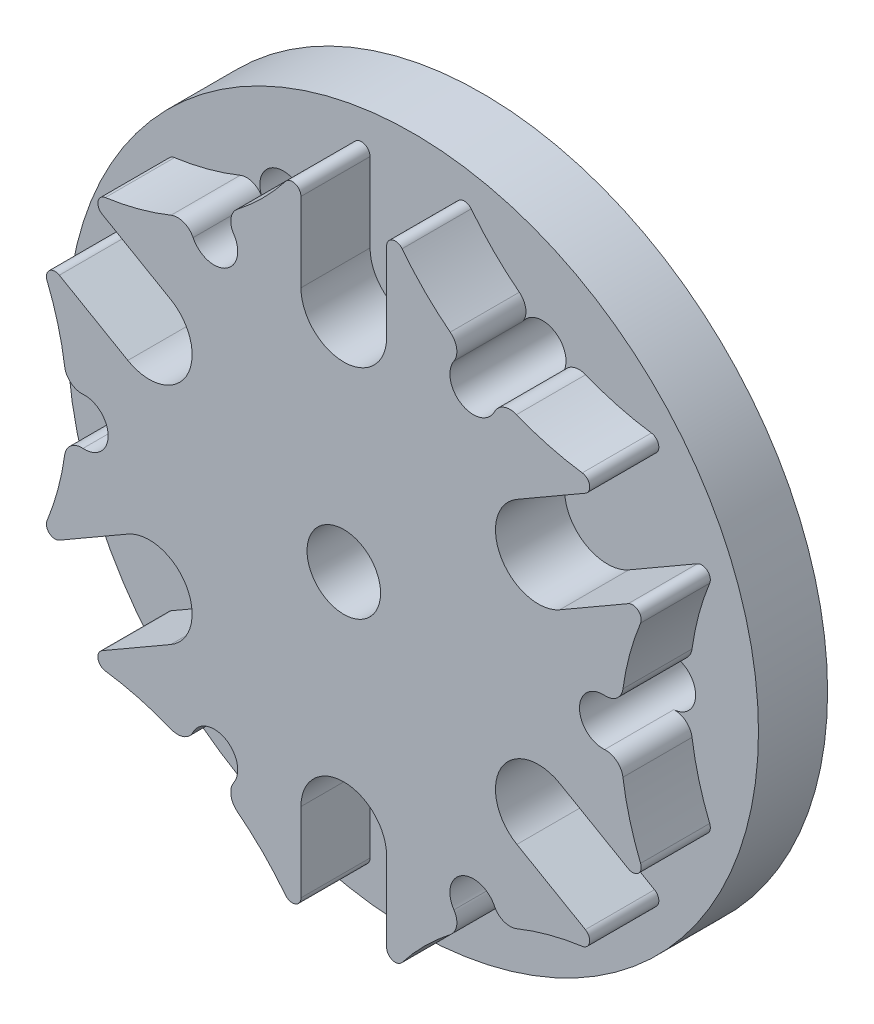
SolidWorks part; units mm, degrees
ref_plane "Front Plane" through (0, 0, 0) normal (0, 0, 1) x (1, 0, 0)
ref_plane "Top Plane" through (0, 0, 0) normal (0, 1, 0) x (1, 0, 0)
ref_plane "Right Plane" through (0, 0, 0) normal (1, 0, 0) x (0, 0, -1)
sketch "Sketch2" plane through (0, 0, 0) normal (0, 0, 1) x (1, 0, 0)
  circle A0 centre (0, 0) radius 31.75
  point P17 (0, 0)
  dimension "D4" = 63.5
extrude "Boss-Extrude1" add sketch "Sketch2" along normal blind 6.35
sketch "Sketch3" plane through (0, 0, 6.35) normal (0, 0, 1) x (1, 0, 0)
  line L0 (0, 30.411) -> (0, 20.6375) construction
  line L1 (3.937, 30.411) -> (3.937, 20.6375)
  line L2 (-3.937, 30.411) -> (-3.937, 20.6375)
  line L5 (24.3682, 18.6151) -> (15.9041, 13.7283)
  line L8 (28.3052, 11.796) -> (19.8411, 6.9092)
  line L11 (26.3367, 15.2055) -> (17.8726, 10.3187) construction
  line L14 (28.3052, -11.796) -> (19.8411, -6.9092)
  line L17 (24.3682, -18.6151) -> (15.9041, -13.7283)
  line L18 (26.3367, -15.2055) -> (17.8726, -10.3187) construction
  line L19 (3.937, -30.411) -> (3.937, -20.6375)
  line L20 (-3.937, -30.411) -> (-3.937, -20.6375)
  line L21 (0, -30.411) -> (0, -20.6375) construction
  line L22 (-24.3682, -18.6151) -> (-15.9041, -13.7283)
  line L23 (-28.3052, -11.796) -> (-19.8411, -6.9092)
  line L24 (-26.3367, -15.2055) -> (-17.8726, -10.3188) construction
  line L25 (-28.3052, 11.796) -> (-19.8411, 6.9092)
  line L26 (-24.3682, 18.6151) -> (-15.9041, 13.7283)
  line L27 (-26.3367, 15.2055) -> (-17.8726, 10.3187) construction
  circle A0 centre (0, 0) radius 20.6375 construction
  arc A1 (3.937, 30.411) -> (-3.937, 30.411) centre (0, 30.411) ccw
  arc A2 (-3.937, 20.6375) -> (3.937, 20.6375) centre (0, 20.6375) ccw
  arc A13 (-3.937, 30.411) -> (-24.3682, 18.6151) centre (-25.4, 43.9941) cw
  arc A14 (28.3052, 11.796) -> (24.3682, 18.6151) centre (26.3367, 15.2055) ccw
  arc A15 (15.9041, 13.7283) -> (19.8411, 6.9092) centre (17.8726, 10.3187) ccw
  arc A16 (24.3682, -18.6151) -> (28.3052, -11.796) centre (26.3367, -15.2055) ccw
  arc A17 (19.8411, -6.9092) -> (15.9041, -13.7283) centre (17.8726, -10.3187) ccw
  arc A18 (-3.937, -30.411) -> (3.937, -30.411) centre (0, -30.411) ccw
  arc A19 (3.937, -20.6375) -> (-3.937, -20.6375) centre (0, -20.6375) ccw
  arc A20 (-28.3052, -11.796) -> (-24.3682, -18.6151) centre (-26.3367, -15.2055) ccw
  arc A21 (-15.9041, -13.7283) -> (-19.8411, -6.9092) centre (-17.8726, -10.3188) ccw
  arc A22 (-24.3682, 18.6151) -> (-28.3052, 11.796) centre (-26.3367, 15.2055) ccw
  arc A23 (-19.8411, 6.9092) -> (-15.9041, 13.7283) centre (-17.8726, 10.3187) ccw
  arc A24 (24.3682, 18.6151) -> (3.937, 30.411) centre (25.4, 43.9941) cw
  arc A25 (28.3052, -11.796) -> (28.3052, 11.796) centre (50.8, 0) cw
  arc A26 (3.937, -30.411) -> (24.3682, -18.6151) centre (25.4, -43.9941) cw
  arc A27 (-24.3682, -18.6151) -> (-3.937, -30.411) centre (-25.4, -43.9941) cw
  arc A28 (-28.3052, 11.796) -> (-28.3052, -11.796) centre (-50.8, 0) cw
  point P5 (0, 25.5243)
  point P10 (-12.7, 21.997)
  point P17 (22.1047, 12.7621)
  point P24 (22.1047, -12.7621)
  point P31 (0, -25.5243)
  point P38 (-22.1047, -12.7621)
  point P45 (-22.1047, 12.7621)
  point P51 (0, 0)
  point P67 (0, 0)
  dimension "D1" = 41.275
  dimension "D2" = 3.937
  dimension "D5" = 25.4
  dimension "D3" = 25.4
  dimension "D4" = 6
  dimension "D6" = 6
extrude "Boss-Extrude2" add sketch "Sketch3" along normal blind 6.35
sketch "Sketch4" plane through (0, 0, 12.7) normal (0, 0, 1) x (1, 0, 0)
  circle A0 centre (0, 0) radius 3.3782
  dimension "D1" = 6.7564
extrude "Cut-Extrude1" cut sketch "Sketch4" against normal through all
fillet "Fillet2" radius 0.7937 12 edges at (-24.3682, 18.6151, 9.525) (-3.937, 30.411, 9.525) (3.937, 30.411, 9.525) (24.3682, 18.6151, 9.525) (28.3052, 11.796, 9.525) (28.3052, -11.796, 9.525) (24.3682, -18.6151, 9.525) (3.937, -30.411, 9.525) (-3.937, -30.411, 9.525) (-28.3052, 11.796, 9.525) (-28.3052, -11.796, 9.525) (-24.3682, -18.6151, 9.525)
sketch "Sketch5" plane through (0, 0, 0) normal (0, 0, -1) x (-1, 0, 0)
  line L0 (-1.0086, 1.747) -> (-22704.1831, 39324.7986) construction
  line L1 (0, 1.3224) -> (0, 50001.3224) construction
  circle A0 centre (0, 0) radius 23.8125 construction
  circle A1 centre (-11.9063, 20.6222) radius 2.159
  circle A2 centre (11.9063, 20.6222) radius 2.159
  circle A3 centre (23.8125, 0) radius 2.159
  circle A4 centre (11.9063, -20.6222) radius 2.159
  circle A5 centre (-11.9062, -20.6222) radius 2.159
  circle A6 centre (-23.8125, 0) radius 2.159
  point P17 (0, 0)
  dimension "D1" = 47.625
  dimension "D2" = 4.318
  dimension "D4" = 30
  dimension "D3" = 6
extrude "Cut-Extrude2" cut sketch "Sketch5" against normal through all
fillet "Fillet3" radius 1.5875 12 edges at (25.4397, -1.419, 9.525) (25.4397, 1.419, 9.525) (13.9487, 21.3219, 9.525) (11.4909, 22.7409, 9.525) (-11.4909, 22.7409, 9.525) (-13.9487, 21.3219, 9.525) (-25.4397, 1.419, 9.525) (-25.4397, -1.419, 9.525) (-13.9487, -21.3219, 9.525) (-11.4909, -22.7409, 9.525) (11.4909, -22.7409, 9.525) (13.9487, -21.3219, 9.525)
